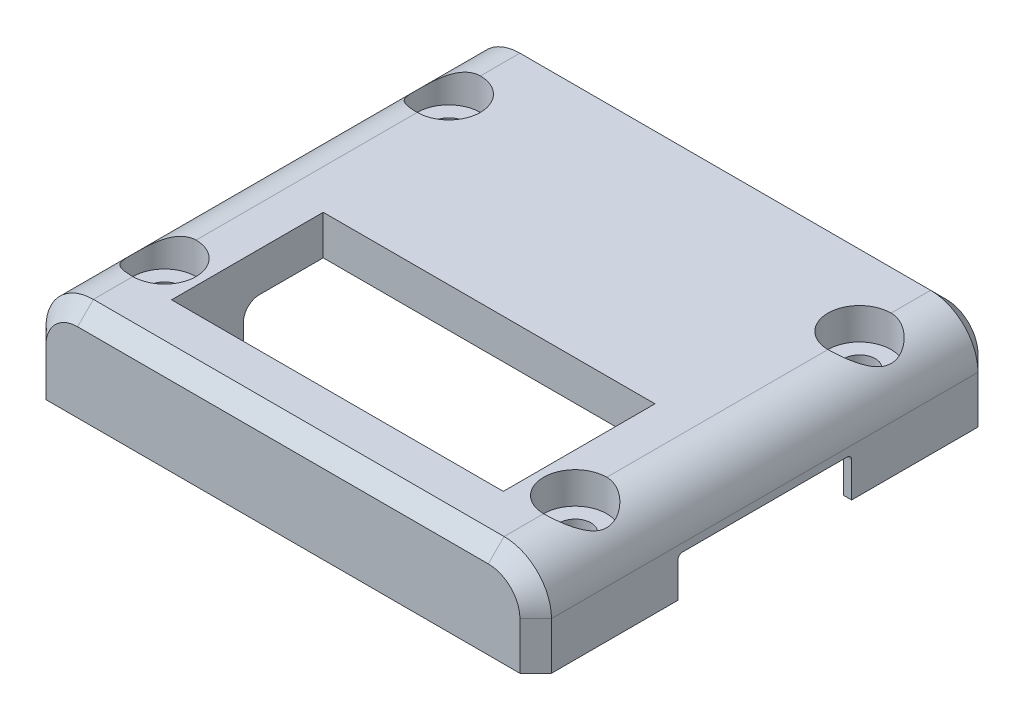
SolidWorks part; units mm, degrees
ref_plane "Front Plane" through (0, 0, 0) normal (0, 0, 1) x (1, 0, 0)
ref_plane "Top Plane" through (0, 0, 0) normal (0, 1, 0) x (1, 0, 0)
ref_plane "Right Plane" through (0, 0, 0) normal (1, 0, 0) x (0, 0, -1)
sketch "Sketch1" plane through (0, 0, 0) normal (0, 1, 0) x (1, 0, 0)
  line L0 (-16, -14.5) -> (16, -14.5)
  line L1 (-16, -14.5) -> (-16, 14.5)
  line L2 (16, -14.5) -> (16, 14.5)
  line L3 (-16, 14.5) -> (16, 14.5)
  line L4 (-16, -14.5) -> (16, 14.5) construction
  line L5 (16, -14.5) -> (-16, 14.5) construction
  point P1 (0, 0)
  dimension "D1" = 32
  dimension "D2" = 29
extrude "Boss-Extrude1" add sketch "Sketch1" along normal blind 6 contours L3 L2 L0 L1
sketch "Sketch2" plane through (0, 6, 0) normal (0, 1, 0) x (1, 0, 0)
  line L0 (-13, -9) -> (13, -9) construction
  line L1 (-13, -9) -> (-13, 9) construction
  line L2 (13, -9) -> (13, 9) construction
  line L3 (-13, 9) -> (13, 9) construction
  line L4 (-13, -9) -> (13, 9) construction
  line L5 (13, -9) -> (-13, 9) construction
  circle A0 centre (-13, 9) radius 1
  circle A1 centre (13, 9) radius 1
  circle A2 centre (13, -9) radius 1
  circle A3 centre (-13, -9) radius 1
  point P1 (0, 0)
  dimension "D1" = 2
  dimension "D2" = 26
  dimension "D3" = 18
extrude "Cut-Extrude1" cut sketch "Sketch2" against normal blind 10
sketch "Sketch3" plane through (0, 6, 0) normal (0, 1, 0) x (1, 0, 0)
  line L0 (0, -6.25) -> (0, 6.25) construction
  line L1 (-10.5, 1.45) -> (10.5, 1.45) construction
  line L2 (-10.5, 1.45) -> (-10.5, 11.05) construction
  line L3 (10.5, 1.45) -> (10.5, 11.05) construction
  line L4 (-10.5, 11.05) -> (10.5, 11.05) construction
  line L5 (-10.5, 1.45) -> (10.5, 11.05) construction
  line L6 (10.5, 1.45) -> (-10.5, 11.05) construction
  line L7 (-10.5, -11.05) -> (10.5, -11.05)
  line L8 (-10.5, -11.05) -> (-10.5, -1.45)
  line L9 (10.5, -11.05) -> (10.5, -1.45)
  line L10 (-10.5, -1.45) -> (10.5, -1.45)
  line L11 (-10.5, -11.05) -> (10.5, -1.45) construction
  line L12 (10.5, -11.05) -> (-10.5, -1.45) construction
  point P4 (0, 0)
  dimension "D1" = 9.6
  dimension "D2" = 21
  dimension "D3" = 12.5
extrude "Cut-Extrude2" cut sketch "Sketch3" against normal blind 10
sketch "Sketch4" plane through (0, 0, 0) normal (0, -1, 0) x (1, 0, 0)
  line L0 (15.5, 13.5) -> (-15.5, 13.5)
  line L1 (15.5, 13.5) -> (15.5, -13.5)
  line L2 (-15.5, 13.5) -> (-15.5, -13.5)
  line L3 (15.5, -13.5) -> (-15.5, -13.5)
  line L4 (15.5, 13.5) -> (-15.5, -13.5) construction
  line L5 (-15.5, 13.5) -> (15.5, -13.5) construction
  line L6 (-16, -14.5) -> (16, -14.5) construction
  point P1 (0, 0)
  dimension "D1" = 31
  dimension "D2" = 1
extrude "Cut-Extrude3" cut sketch "Sketch4" against normal blind 1
fillet "Fillet2" radius 3 2 edges at (-16, 6, 0) (16, 6, 0)
sketch "Sketch5" plane through (0, 6, 0) normal (0, 1, 0) x (1, 0, 0)
  circle A0 centre (-13, 9) radius 2
  circle A1 centre (13, 9) radius 2
  circle A2 centre (13, -9) radius 2
  circle A3 centre (-13, -9) radius 2
  dimension "D1" = 4
extrude "Cut-Extrude4" cut sketch "Sketch5" against normal blind 2
chamfer "Chamfer2" distance 1 angle 45 10 edges at (-16, 1.5, 14.5) (-15.1213, 5.1213, 14.5) (0, 6, 14.5) (15.1213, 5.1213, 14.5) (16, 1.5, 14.5) (-16, 1.5, -14.5) (-15.1213, 5.1213, -14.5) (0, 6, -14.5) (15.1213, 5.1213, -14.5) (16, 1.5, -14.5)
sketch "Sketch6" plane through (0, 0, 0) normal (0, -1, 0) x (1, 0, 0)
  line L0 (-15.5, 13.5) -> (-15.5, -13.5) construction
  line L1 (-15, -5.5) -> (-16, -5.5)
  line L2 (-15, -5.5) -> (-15, 5.5)
  line L3 (-15, 5.5) -> (-16, 5.5)
  line L4 (-16, -5.5) -> (-16, 5.5)
  line L5 (-15, -5.5) -> (-16, 5.5) construction
  line L6 (-15, 5.5) -> (-16, -5.5) construction
  line L7 (-16, 13.5) -> (-16, -13.5) construction
  line L8 (15.5, -13.5) -> (15.5, 13.5) construction
  line L9 (15, -5.5) -> (16, -5.5)
  line L10 (15, -5.5) -> (15, 5.5)
  line L11 (15, 5.5) -> (16, 5.5)
  line L12 (16, -5.5) -> (16, 5.5)
  line L13 (15, -5.5) -> (16, 5.5) construction
  line L14 (15, 5.5) -> (16, -5.5) construction
  line L15 (16, 13.5) -> (16, -13.5) construction
  point P0 (-15.5, 0)
  point P9 (15.5, 0)
  dimension "D1" = 11
extrude "Cut-Extrude5" cut sketch "Sketch6" against normal blind 2.5
fillet "Fillet3" radius 0.3 4 edges at (15.5, 2.5, 5.5) (15.5, 2.5, -5.5) (-15.5, 2.5, -5.5) (-15.5, 2.5, 5.5)
sketch "Sketch7" plane through (0, 1, 0) normal (0, -1, 0) x (1, 0, 0)
  line L0 (-15.5, 13.5) -> (-15.5, 5.5) construction
  line L1 (15.5, -6.5) -> (-15.5, -6.5)
  line L2 (15.5, -6.5) -> (15.5, 6.5)
  line L3 (15.5, 6.5) -> (-15.5, 6.5)
  line L4 (-15.5, -6.5) -> (-15.5, 6.5)
  line L5 (15.5, -6.5) -> (-15.5, 6.5) construction
  line L6 (15.5, 6.5) -> (-15.5, -6.5) construction
  point P0 (0, 0)
  dimension "D1" = 13
extrude "Cut-Extrude6" cut sketch "Sketch7" against normal blind 2.5
fillet "Fillet4" radius 1 3 edges at (0, 3.5, -6.5) (13, 3.5, 6.5) (-13, 3.5, 6.5)
sketch "Эскиз1" plane through (0, 1, 0) normal (0, -1, 0) x (1, 0, 0)
  line L0 (-10.5, 1.45) -> (-10.5, 5.5) construction
  line L1 (-10.5, -1.45) -> (10.5, -1.45)
  line L2 (-10.5, -1.45) -> (-10.5, -13.5)
  line L3 (-10.5, -13.5) -> (10.5, -13.5)
  line L4 (10.5, -1.45) -> (10.5, -13.5)
  line L5 (-10.5, -1.45) -> (10.5, -13.5) construction
  line L6 (-10.5, -13.5) -> (10.5, -1.45) construction
  line L7 (10.5, 5.5) -> (10.5, 1.45) construction
  line L8 (-15.5, -13.5) -> (15.5, -13.5) construction
  line L9 (0, 0) -> (5.1222, 0) construction
  line L10 (10.5, 1.45) -> (-10.5, 1.45) construction
  point P0 (0, -7.475)
extrude "Вырез-Вытянуть1" cut sketch "Эскиз1" against normal up to surface (2.5 mm away) up to face at (0, 3.5, 1.7375)
fillet "Скругление1" radius 1 2 edges at (10.5, 3.5, -9.5) (-10.5, 3.5, -9.5)
sketch "Эскиз2" plane through (0, 0, -13.5) normal (0, 0, 1) x (1, 0, 0)
  line L0 (-15, 0) -> (15, 0) construction
  line L1 (-5.5, 2.5) -> (5.5, 2.5)
  line L2 (-5.5, 2.5) -> (-5.5, 0)
  line L3 (-5.5, 0) -> (5.5, 0)
  line L4 (5.5, 2.5) -> (5.5, 0)
  line L5 (-5.5, 2.5) -> (5.5, 0) construction
  line L6 (-5.5, 0) -> (5.5, 2.5) construction
  line L7 (0, 0) -> (0, 5) construction
  line L8 (13, 5) -> (-13, 5) construction
  point P0 (0, 1.25)
  dimension "D1" = 11
  dimension "D2" = 2.5
extrude "Вырез-Вытянуть2" cut sketch "Эскиз2" against normal through all
fillet "Скругление2" radius 0.3 2 edges at (-5.5, 2.5, -14) (5.5, 2.5, -14)
equation "\"motor_diameter\"= 30"
equation "\"mm_diameter\"= IIF ( \"motor_diameter\" < 34 , 41 , \"motor_diameter\" + 8 )"
equation "\"upper_shafts_diameter\"= 5"
equation "\"upper_shats_length\"= 180"
equation "\"upper_bearing_d1\"= 10"
equation "\"upper_bearing_d2\"= 5"
equation "\"upper_bearing_h\"= 15"
equation "\"lower_shafts_diameter\"= 5"
equation "\"lower_shafts_length\"= 180"
equation "\"lower_bearing_d1\"= 10"
equation "\"lower_bearing_d2\"= 5"
equation "\"lower_bearing_h\"= 15"
equation "\"print_offset\"= 0.2"
equation "\"bh_screws_d\"= 2"
equation "\"bh_screws_h\"= 20"
equation "\"bh_screws_hh_d\"= 3.4"
equation "\"bh_screws_hh_h\"= 2"
equation "\"bh_nut_d\"= 3.8"
equation "\"bh_nut_h\"= 2"
equation "\"motor_screws_d\"= 3"
equation "\"motor_screws_h\"= 16"
equation "\"motor_screws_hh_d\"= 5.5"
equation "\"motor_screws_hh_h\"= 3"
equation "\"plate_hole_distance\"= 25.4"
equation "\"plate_screws_d\"= 6.5"
equation "\"shafts_diameter\"= IIF ( \"mm_diameter\" < 42 , 42 + 8 , \"mm_diameter\" + 8 )"
equation "\"central_hole_diameter\"= 8"
equation "\"bh_thikness\"= 4"
equation "\"D2@Sketch1\"=\"upper_bearing_h\"+\"bh_thikness\"*2+3*2"
